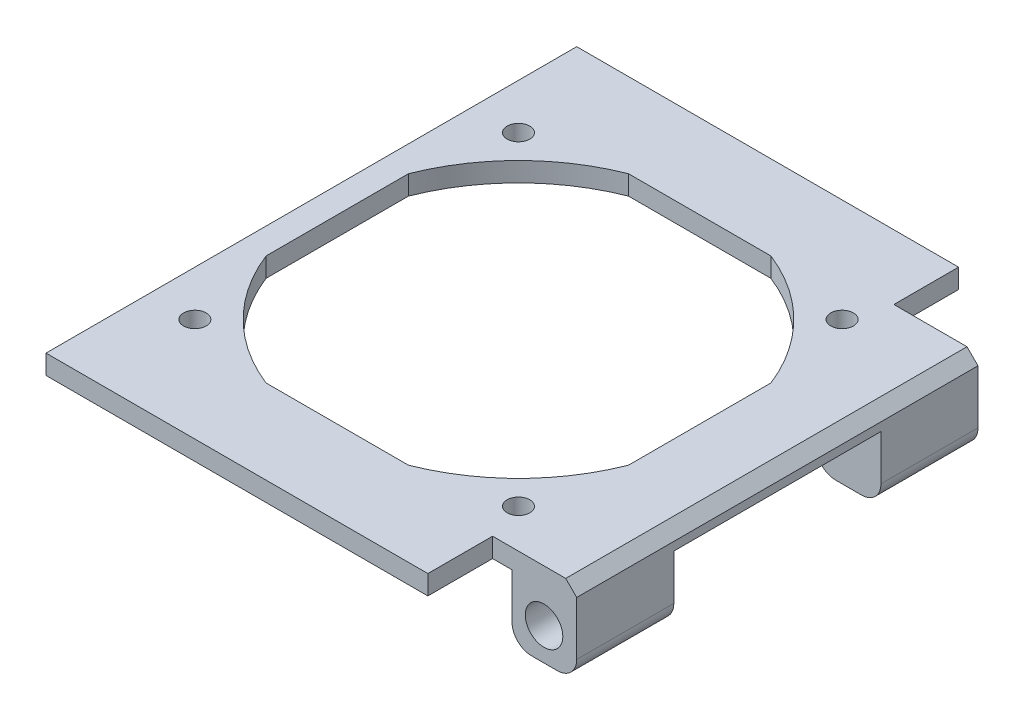
SolidWorks part; units mm, degrees
ref_plane "Front Plane" through (0, 0, 0) normal (0, 0, 1) x (1, 0, 0)
ref_plane "Top Plane" through (0, 0, 0) normal (0, 1, 0) x (1, 0, 0)
ref_plane "Right Plane" through (0, 0, 0) normal (1, 0, 0) x (0, 0, -1)
sketch "Sketch1" plane through (0, 0, 0) normal (0, 1, 0) x (1, 0, 0)
  line L0 (59, 82) -> (59, 72)
  line L1 (0, 0) -> (72, 0)
  line L2 (0, 0) -> (0, 82)
  line L3 (0, 82) -> (72, 82)
  line L4 (72, 0) -> (72, 82)
  line L5 (59, 72) -> (72, 72)
  line L6 (72, 10) -> (59, 10)
  line L7 (59, 10) -> (59, 0)
  dimension "D1" = 82
  dimension "D2" = 72
  dimension "D3" = 10
  dimension "D4" = 13
extrude "Boss-Extrude1" add sketch "Sketch1" along normal blind 3 contours L7 L6 L4 L5 L0 L3 L2 L1 region at (34.641, 0, -41)
sketch "Sketch2" plane through (0, 0, 0) normal (0, -1, 0) x (1, 0, 0)
  line L0 (70, -41) -> (0, -41) construction
  line L5 (72, -10) -> (72, -72) construction
  line L12 (72, -72) -> (62, -72)
  line L13 (72, -72) -> (72, -57)
  line L14 (72, -57) -> (62, -57)
  line L15 (62, -72) -> (62, -57)
  line L16 (62, -10) -> (62, -25)
  line L17 (72, -25) -> (62, -25)
  line L18 (72, -10) -> (72, -25)
  line L19 (72, -10) -> (62, -10)
  line L20 (0, -82) -> (59, -82) construction
  dimension "D1" = 10
  dimension "D2" = 10
  dimension "D3" = 15
extrude "Boss-Extrude2" add sketch "Sketch2" along normal blind 10
sketch "Sketch4" plane through (0, 3, 0) normal (0, 1, 0) x (1, 0, 0)
  line L0 (72, 41) -> (0, 41) construction
  line L2 (0, 82) -> (59, 82) construction
  line L3 (60, 52) -> (60, 30)
  line L13 (4, 52) -> (4, 30)
  line L17 (43, 69) -> (21, 69)
  line L23 (21, 13) -> (43, 13)
  line L25 (32, 41) -> (32, 88.0264) construction
  line L26 (0, 0) -> (0, 82) construction
  arc A0 (21, 69) -> (4, 52) centre (32, 41) ccw
  arc A1 (60, 52) -> (43, 69) centre (32, 41) ccw
  arc A2 (43, 13) -> (60, 30) centre (32, 41) ccw
  arc A3 (4, 30) -> (21, 13) centre (32, 41) ccw
  circle A4 centre (57, 66) radius 1.75
  circle A5 centre (57, 16) radius 1.75
  circle A6 centre (7, 16) radius 1.75
  circle A7 centre (7, 66) radius 1.75
  dimension "D6" = 3.5
  dimension "D2" = 56
  dimension "D3" = 22
  dimension "D4" = 4
  dimension "D7" = 25
  dimension "D8" = 25
  dimension "D10" = 41
extrude "Cut-Extrude1" cut sketch "Sketch4" against normal through all contours L13 A3 L23 A2 L3 A1 L17 A0 | A7 | A4 | A5 | A6 region at (32, 3, -41) region at (57, 3, -66) region at (57, 3, -16) region at (7, 3, -16) region at (7, 3, -66)
fillet "Fillet1" radius 3 4 edges at (72, -10, -64.5) (62, -10, -64.5) (72, -10, -17.5) (62, -10, -17.5)
sketch "Sketch6" plane through (0, 0, -57) normal (0, 0, 1) x (1, 0, 0)
  line L0 (66.9487, -5) -> (66.9487, 0) construction
  line L1 (0, 0) -> (59, 0) construction
  line L5 (69, -10) -> (65, -10) construction
  circle A0 centre (66.9487, -5) radius 2.9
  dimension "D1" = 5.8
  dimension "D2" = 5
extrude "Cut-Extrude4" cut sketch "Sketch6" along normal offset from surface (11 mm away) 4 from surface up to face at (67, -5.8738, -57) starting at face at (65, -3.6553, -72)
extrude "Cut-Extrude5" cut sketch "Sketch6<2>" against normal offset from surface (11 mm away) 4 from surface up to face at (67, -5.8738, -25) starting at face at (65, -3.6553, -10)
sketch "Sketch6<2>" plane through (0, 0, -57) normal (0, 0, 1) x (1, 0, 0) same geometry as "Sketch6"
chamfer "Chamfer1" distance 1.7 angle 45 1 edges at (72, 3, -41)
sketch "Sketch9" plane through (0, 0, 0) normal (0, -1, 0) x (1, 0, 0)
  line L0 (5, 0) -> (5, -82) construction
  line L4 (0, 0) -> (0, -82) construction
  line L5 (0, 0) -> (59, 0) construction
  line L6 (0, -82) -> (59, -82) construction
  circle A0 centre (5, -5) radius 3.1
  circle A1 centre (5, -77) radius 3.1
  dimension "D1" = 6.2
  dimension "D2" = 6.2
  dimension "D3" = 5
  dimension "D4" = 5
  dimension "D5" = 5
extrude "Cut-Extrude7" cut sketch "Sketch9" against normal blind 1.5
